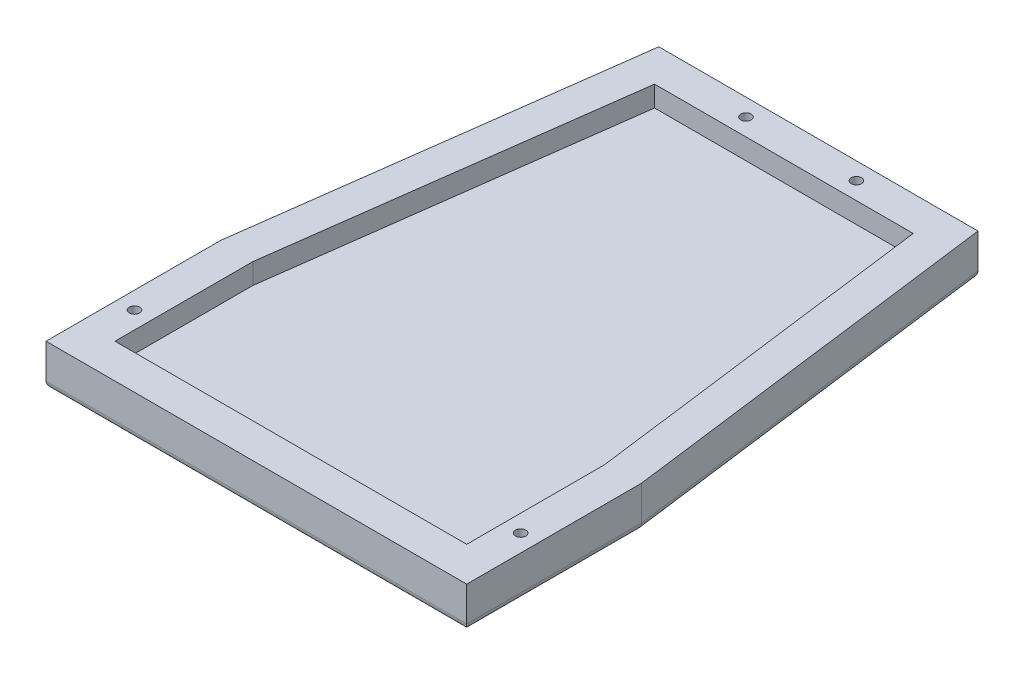
SolidWorks part; units mm, degrees
ref_plane "Płaszczyzna przednia" through (0, 0, 0) normal (0, 0, 1) x (1, 0, 0)
ref_plane "Płaszczyzna górna" through (0, 0, 0) normal (0, 1, 0) x (1, 0, 0)
ref_plane "Płaszczyzna prawa" through (0, 0, 0) normal (1, 0, 0) x (0, 0, -1)
sketch "Szkic1" plane through (0, 0, 0) normal (0, 1, 0) x (1, 0, 0)
  line L0 (-46.2252, 44.9878) -> (-0.2252, 44.9878)
  line L1 (-0.2252, 44.9878) -> (7.2748, -12.8855)
  line L2 (7.2748, -12.8855) -> (7.2748, -36.4122)
  line L3 (7.2748, -36.4122) -> (-53.7252, -36.4122)
  line L4 (-53.7252, -36.4122) -> (-53.7252, -11.4122)
  line L5 (-53.7252, -11.4122) -> (-46.2252, 44.9878)
  dimension "D1" = 46
  dimension "D2" = 61
  dimension "D3" = 7.5
  dimension "D4" = 56.4
  dimension "D5" = 25
  dimension "D6" = 7.5
extrude "Dodanie-wyciągnięcie1" add sketch "Szkic1" along normal blind 3
sketch "Szkic3" plane through (0, 0, 0) normal (0, 1, 0) x (1, 0, 0)
  line L0 (-48.7252, -31.4122) -> (2.2748, -31.4122)
  line L1 (-53.7252, -11.4122) -> (-53.7252, -36.4122) construction
  line L2 (7.2748, -36.4122) -> (7.2748, -12.8855) construction
  line L3 (-48.7252, -31.4122) -> (-48.7252, -11.4122)
  line L4 (-53.7252, -36.4122) -> (7.2748, -36.4122) construction
  line L5 (-41.8901, 39.9878) -> (-4.3863, 39.9878)
  line L6 (-0.2252, 44.9878) -> (-46.2252, 44.9878) construction
  line L7 (-4.3863, 39.9878) -> (2.2748, -11.4122)
  line L8 (-48.7252, -11.4122) -> (-41.8901, 39.9878)
  line L9 (2.2748, -31.4122) -> (2.2748, -11.4122)
  line L10 (-46.2252, 44.9878) -> (-53.7252, -11.4122) construction
  line L11 (7.2748, -12.8855) -> (-0.2252, 44.9878) construction
  dimension "D1" = 51
  dimension "D2" = 5
  dimension "D3" = 5
  dimension "D4" = 5
  dimension "D5" = 20
  dimension "D6" = 5
  dimension "D7" = 0
  dimension "D8" = 0
  dimension "D9" = 20
extrude "Wyciągnięcie-cienka ścianka1" add sketch "Szkic3" along normal blind 6 from offset 0 thin contours L7 L9 L0 L3 L8 L5 thin type one direction wall 5
sketch "Szkic5" plane through (0, 6, 0) normal (0, 1, 0) x (1, 0, 0)
  line L0 (-46.2692, 44.9878) -> (0.0075, 44.9878) construction
  line L1 (7.2748, -36.4122) -> (7.2748, -11.0896) construction
  line L2 (-53.7252, -36.4122) -> (-53.7252, -11.0812) construction
  circle A0 centre (-31.1292, 42.4878) radius 0.75
  circle A1 centre (-15.1292, 42.4878) radius 0.75
  circle A2 centre (-51.2252, -26.0812) radius 0.75
  circle A3 centre (4.7748, -26.0896) radius 0.75
  point P17 (0, 0)
  dimension "D3" = 1.5
  dimension "D4" = 1.5
  dimension "D8" = 1.5
  dimension "D9" = 1.5
  dimension "D1" = 2.5
  dimension "D2" = 2.5
  dimension "D5" = 16
  dimension "D6" = 15.14
  dimension "D7" = 15.1368
  dimension "D10" = 2.5
  dimension "D11" = 2.5
  dimension "D12" = 15
  dimension "D13" = 15
  dimension "D14" = 10.7609
  dimension "D15" = 10.7429
extrude "Wytnij-wyciągnięcie1" cut sketch "Szkic5" against normal blind 39 and the other way blind 51
fillet "Zaokrąglenie1" radius 1 10 edges at (-23.1308, 0, -44.9878) (-49.9972, 0, -16.9533) (-53.7252, 0, 23.7467) (-23.2252, 0, 36.4122) (7.2748, 0, 23.7509) (3.6412, 0, -16.9491) (-31.1292, 0, -43.2378) (-15.1292, 0, -43.2378) (4.7748, 0, 25.3396) (-51.2252, 0, 25.3312)
